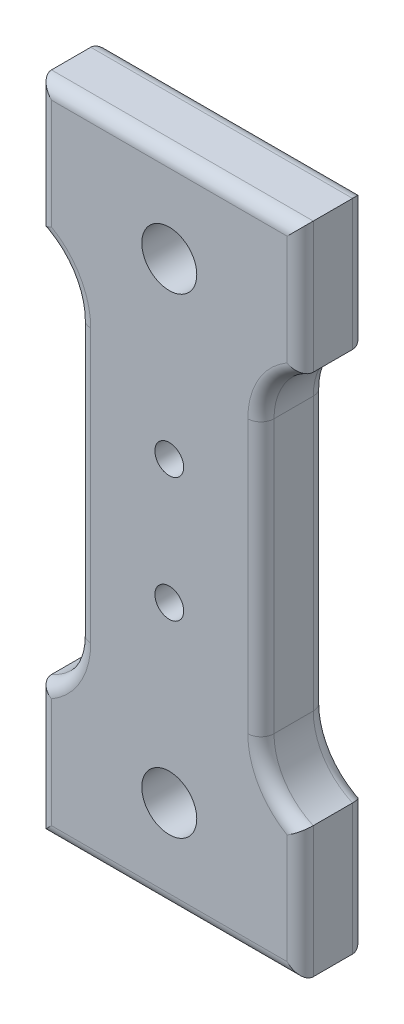
SolidWorks part; units mm, degrees
ref_plane "Front Plane" through (0, 0, 0) normal (0, 0, 1) x (1, 0, 0)
ref_plane "Top Plane" through (0, 0, 0) normal (0, 1, 0) x (1, 0, 0)
ref_plane "Right Plane" through (0, 0, 0) normal (1, 0, 0) x (0, 0, -1)
sketch "Sketch1" plane through (0, 0, 0) normal (0, 0, 1) x (1, 0, 0)
  line L0 (0, 0) -> (20, 0)
  line L1 (0, 0) -> (0, 50)
  line L2 (20, 0) -> (20, 50)
  line L3 (0, 50) -> (20, 50)
  dimension "D1" = 20
  dimension "D2" = 50
extrude "Boss-Extrude1" add sketch "Sketch1" along normal blind 5
sketch "Sketch2" plane through (0, 0, 5) normal (0, 0, 1) x (1, 0, 0)
  line L0 (10, 50) -> (10, 0) construction
  line L1 (20, 50) -> (0, 50) construction
  line L2 (0, 0) -> (20, 0) construction
  line L3 (20, 25) -> (0, 25) construction
  line L4 (20, 0) -> (20, 50) construction
  line L5 (0, 50) -> (0, 0) construction
  line L6 (10, 29.75) -> (10, 20.25) construction
  circle A0 centre (10, 43) radius 2.1
  circle A1 centre (10, 7) radius 2.1
  circle A2 centre (10, 29.75) radius 1.1
  circle A3 centre (10, 20.25) radius 1.1
  point P20 (10, 25)
  dimension "D1" = 7
  dimension "D3" = 4.2
  dimension "D4" = 4.2
  dimension "D5" = 9.5
  dimension "D6" = 2.2
  dimension "D7" = 2.2
  dimension "D2" = 7
extrude "Cut-Extrude1" cut sketch "Sketch2" against normal through all
sketch "Sketch3" plane through (0, 0, 5) normal (0, 0, 1) x (1, 0, 0)
  line L0 (0, 40) -> (3, 40)
  line L1 (0, 40) -> (0, 10)
  line L2 (3, 40) -> (3, 10)
  line L3 (0, 10) -> (3, 10)
  line L4 (0, 50) -> (0, 0) construction
  line L5 (3, 25) -> (0, 25) construction
  line L6 (20, 25) -> (0, 25) construction
  line L7 (20, 0) -> (20, 50) construction
  dimension "D1" = 30
  dimension "D2" = 3
sketch "Sketch4" plane through (0, 0, 5) normal (0, 0, 1) x (1, 0, 0)
  line L0 (10, 50) -> (10, 0) construction
  line L1 (20, 50) -> (0, 50) construction
  line L2 (0, 0) -> (20, 0) construction
ref_plane "Plane1" through (10, 0, 0) normal (-1, 0, 0) x (0, -1, 0)
extrude "Cut-Extrude2" cut sketch "Sketch3" against normal through all
fillet "Fillet1" radius 5 2 edges at (3, 10, 2.5) (3, 40, 2.5)
mirror "Mirror1" about plane through (10, 0, 0) normal (-1, 0, 0) of "Fillet1", "Cut-Extrude2"
fillet "Fillet3" radius 1 24 edges at (2.1833, 11.844, 0) (2.1833, 38.156, 0) (17.8167, 11.844, 0) (17.8167, 38.156, 0) (2.1833, 11.844, 5) (2.1833, 38.156, 5) (17.8167, 11.844, 5) (17.8167, 38.156, 5) (0, 5, 0) (3, 25, 0) (10, 0, 0) (20, 5, 0) (17, 25, 0) (20, 45, 0) (10, 50, 0) (0, 45, 0) (20, 5, 5) (10, 0, 5) (0, 5, 5) (0, 45, 5) (3, 25, 5) (17, 25, 5) (20, 45, 5) (10, 50, 5)
